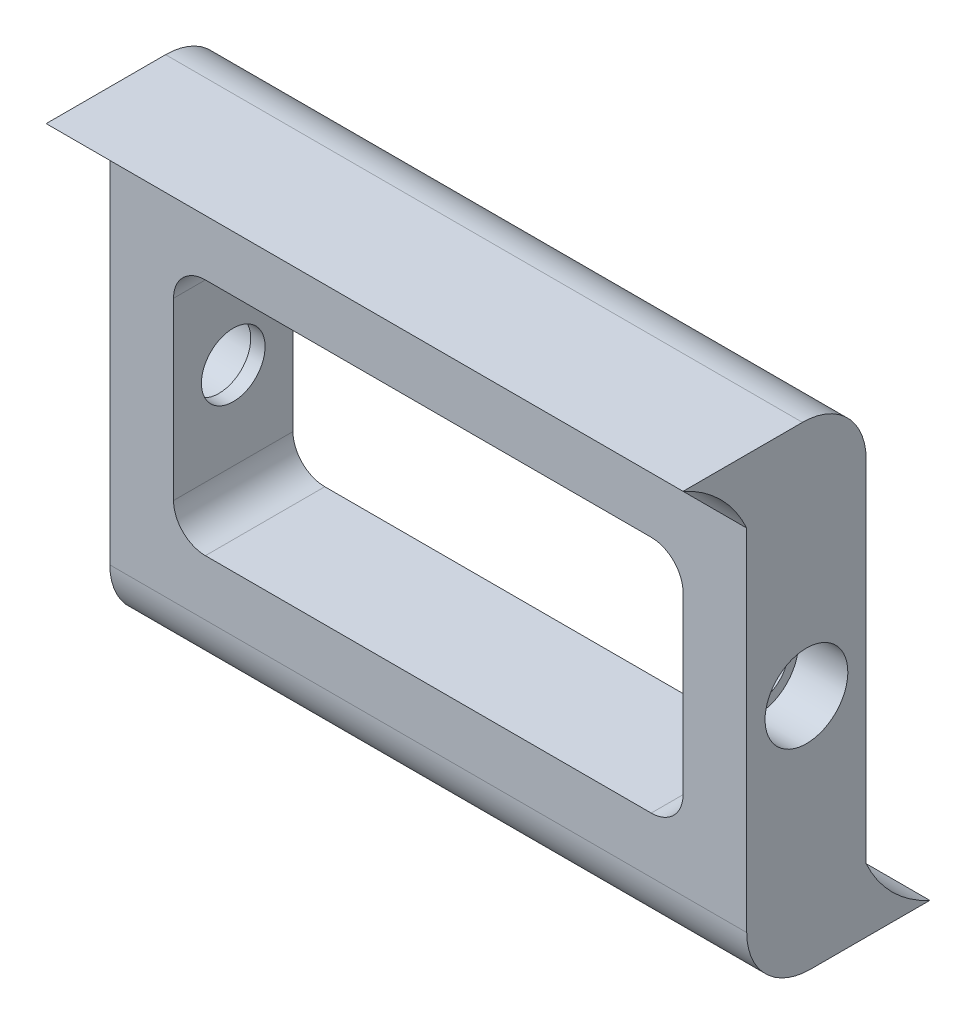
SolidWorks part; units mm, degrees
material "AISI 1020"
ref_plane "Front Plane" through (0, 0, 0) normal (0, 0, 1) x (1, 0, 0)
ref_plane "Top Plane" through (0, 0, 0) normal (0, 1, 0) x (1, 0, 0)
ref_plane "Right Plane" through (0, 0, 0) normal (1, 0, 0) x (0, 0, -1)
sketch "Sketch1" plane through (0, 0, 0) normal (0, 0, 1) x (1, 0, 0)
  line L1 (0, 0) -> (101.6, 0)
  line L2 (0, 0) -> (0, 76.2)
  line L3 (0, 76.2) -> (101.6, 76.2)
  line L4 (101.6, 0) -> (101.6, 76.2)
  dimension "D1" = 76.2
  dimension "D2" = 101.6
extrude "Boss-Extrude1" add sketch "Sketch1" along normal blind 19.05
sketch "Sketch8" [suppressed] plane through (0, 0, 19.05) normal (0, 0, 1) x (1, 0, 0)
  line L0 (10.16, 66.04) -> (91.44, 66.04)
  line L1 (10.16, 66.04) -> (10.16, 10.16)
  line L2 (91.44, 66.04) -> (91.44, 10.16)
  line L3 (10.16, 10.16) -> (91.44, 10.16)
  line L4 (0, 76.2) -> (0, 0) construction
  line L5 (101.6, 0) -> (101.6, 76.2) construction
  line L6 (101.6, 76.2) -> (0, 76.2) construction
  line L7 (0, 0) -> (101.6, 0) construction
  dimension "D1" = 10.16
  dimension "D2" = 10.16
  dimension "D3" = 10.16
  dimension "D4" = 10.16
extrude "Cut-Extrude5" [suppressed] cut sketch "Sketch8" against normal up to surface (19.05 mm away) up to face at (50.8, 38.1, 0)
sketch "Sketch9" [suppressed] plane through (0, 0, 0) normal (-1, 0, 0) x (0, 0, 1)
  line L0 (0, 76.2) -> (0, 66.04)
  line L1 (0, 76.2) -> (-10.16, 76.2)
  line L2 (19.05, 0) -> (19.05, 10.16)
  line L3 (19.05, 0) -> (29.21, 0)
  arc A0 (-10.16, 76.2) -> (0, 66.04) centre (-18.5204, 57.6796) cw
  arc A1 (29.21, 0) -> (19.05, 10.16) centre (37.5704, 18.5204) cw
  dimension "D1" = 20.32
  dimension "D3" = 20.32
  dimension "D2" = 10.16
  dimension "D4" = 10.16
sketch "Sketch3" plane through (0, 0, 19.05) normal (0, 0, 1) x (1, 0, 0)
  line L0 (10.16, 57.15) -> (91.44, 57.15)
  line L1 (91.44, 57.15) -> (91.44, 19.05)
  line L2 (91.44, 19.05) -> (10.16, 19.05)
  line L3 (10.16, 19.05) -> (10.16, 57.15)
  line L4 (101.6, 76.2) -> (0, 76.2) construction
  line L5 (101.6, 0) -> (101.6, 76.2) construction
  line L6 (0, 0) -> (101.6, 0) construction
  line L7 (0, 76.2) -> (0, 0) construction
  dimension "D1" = 19.05
  dimension "D2" = 10.16
  dimension "D3" = 19.05
  dimension "D4" = 10.16
extrude "Cut-Extrude1" cut sketch "Sketch3" against normal blind 25.4
sketch "Sketch4" plane through (101.6, 0, 0) normal (1, 0, 0) x (0, 0, -1)
  line L0 (-19.05, 76.2) -> (-19.05, 66.04)
  line L1 (-19.05, 0) -> (-19.05, 76.2) construction
  line L2 (-19.05, 76.2) -> (-29.21, 76.2)
  line L3 (0, 0) -> (0, 10.16)
  line L4 (0, 0) -> (0, 76.2) construction
  line L5 (0, 0) -> (10.16, 0)
  arc A0 (-29.21, 76.2) -> (-19.05, 66.04) centre (-37.5704, 57.6796) cw
  arc A1 (0, 10.16) -> (10.16, 0) centre (18.5204, 18.5204) ccw
  dimension "D1" = 20.32
  dimension "D2" = 20.32
  dimension "D3" = 10.16
  dimension "D4" = 10.16
  dimension "D5" = 10.16
  dimension "D6" = 10.16
extrude "Boss-Extrude2" add sketch "Sketch4" against normal up to surface (101.6 mm away) up to face at (0, 38.1, 9.525)
fillet "Fillet1" radius 10.16 2 edges at (50.8, 0, 19.05) (50.8, 76.2, 0)
fillet "Fillet2" radius 5.08 4 edges at (91.44, 19.05, 9.525) (10.16, 19.05, 9.525) (91.44, 57.15, 9.525) (10.16, 57.15, 9.525)
sketch "Sketch5" plane through (101.6, 0, 0) normal (1, 0, 0) x (0, 0, -1)
  line L0 (-29.21, 76.2) -> (-10.16, 76.2) construction
  line L1 (0, 10.16) -> (0, 66.04) construction
  circle A0 centre (-9.525, 38.1) radius 6.604
  dimension "D1" = 13.208
  dimension "D2" = 38.1
  dimension "D3" = 9.525
extrude "Cut-Extrude2" cut sketch "Sketch5" against normal blind 7.874
sketch "Sketch6" plane through (0, 0, 0) normal (-1, 0, 0) x (0, 0, 1)
  line L0 (29.21, 76.2) -> (10.16, 76.2) construction
  line L1 (19.05, 66.04) -> (19.05, 10.16) construction
  circle A0 centre (9.525, 38.1) radius 6.604
  dimension "D1" = 13.208
  dimension "D2" = 38.1
  dimension "D3" = 9.525
extrude "Cut-Extrude3" cut sketch "Sketch6" against normal blind 7.874
sketch "Sketch7" plane through (7.874, 0, 0) normal (-1, 0, 0) x (0, 0, 1)
  line L0 (29.21, 76.2) -> (10.16, 76.2) construction
  line L1 (19.05, 66.04) -> (19.05, 10.16) construction
  circle A0 centre (9.525, 38.1) radius 5.08
  dimension "D1" = 10.16
  dimension "D2" = 38.1
  dimension "D3" = 9.525
extrude "Cut-Extrude4" cut sketch "Sketch7" against normal up to surface (85.852 mm away) up to face at (93.726, 44.704, 9.525)
extrude "Boss-Extrude3" [suppressed] add sketch "Sketch9" against normal up to surface (101.6 mm away) up to face at (101.6, 44.704, 9.525)
fillet "Fillet3" [suppressed] radius 10.16
fillet "Fillet4" [suppressed] radius 5.08
sketch "Sketch10" [suppressed] plane through (0, 0, 0) normal (-1, 0, 0) x (0, 0, 1)
  line L0 (8.89, 76.2) -> (-10.16, 76.2) construction
  line L1 (19.05, 66.04) -> (19.05, 10.16) construction
  circle A0 centre (9.525, 38.1) radius 6.604
  dimension "D1" = 13.208
  dimension "D2" = 38.1
  dimension "D3" = 9.525
extrude "Cut-Extrude6" [suppressed] cut sketch "Sketch10" against normal blind 7.874
sketch "Sketch11" [suppressed] plane through (101.6, 0, 0) normal (1, 0, 0) x (0, 0, -1)
  line L0 (-8.89, 76.2) -> (10.16, 76.2) construction
  line L1 (0, 10.16) -> (0, 66.04) construction
  circle A0 centre (-9.525, 38.1) radius 6.604
  dimension "D1" = 13.208
  dimension "D2" = 38.1
  dimension "D3" = 9.525
extrude "Cut-Extrude7" [suppressed] cut sketch "Sketch11" against normal blind 7.874
sketch "Sketch12" [suppressed] plane through (93.726, 0, 0) normal (1, 0, 0) x (0, 0, -1)
  circle A0 centre (-9.525, 38.1) radius 5.08
  dimension "D1" = 10.16
extrude "Cut-Extrude8" [suppressed] cut sketch "Sketch12" against normal up to surface (85.852 mm away) up to face at (7.874, 33.02, 9.525)
